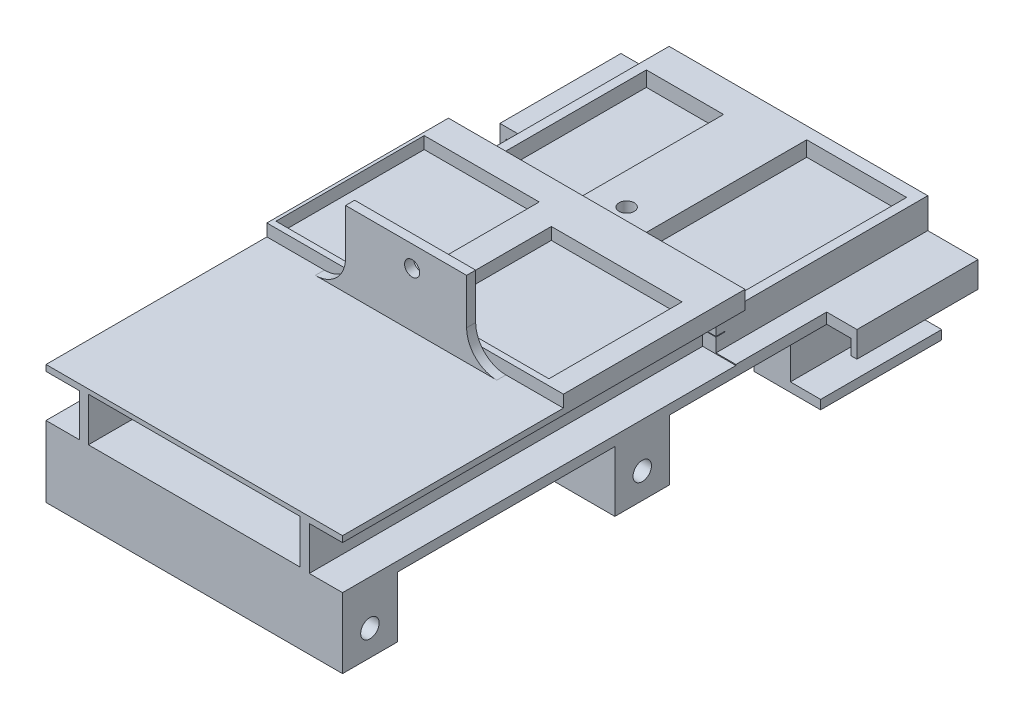
SolidWorks part; units mm, degrees
ref_plane "Front Plane" through (0, 0, 0) normal (0, 0, 1) x (1, 0, 0)
ref_plane "Top Plane" through (0, 0, 0) normal (0, 1, 0) x (1, 0, 0)
ref_plane "Right Plane" through (0, 0, 0) normal (1, 0, 0) x (0, 0, -1)
sketch "Sketch1" plane through (0, 0, 0) normal (0, 1, 0) x (1, 0, 0)
  line L2 (48.0496, -78.5461) -> (-51.9504, -78.5461)
  line L3 (48.0496, -78.5461) -> (48.0496, 121.4539)
  line L4 (48.0496, 121.4539) -> (-51.9504, 121.4539)
  line L5 (-51.9504, -78.5461) -> (-51.9504, 121.4539)
  dimension "D1" = 100
  dimension "D2" = 200
extrude "Boss-Extrude3" add sketch "Sketch1" along normal blind 20
sketch "Sketch2" plane through (0, 0, 78.5461) normal (0, 0, 1) x (1, 0, 0)
  line L0 (-51.9504, 0) -> (48.0496, 0) construction
  line L1 (-36.9504, 18.5) -> (33.0496, 18.5)
  line L2 (-36.9504, 18.5) -> (-36.9504, 4)
  line L3 (-36.9504, 4) -> (33.0496, 4)
  line L4 (33.0496, 18.5) -> (33.0496, 4)
  line L5 (48.0496, 20) -> (48.0496, 0) construction
  dimension "D1" = 14.5
  dimension "D2" = 4
  dimension "D3" = 15
  dimension "D4" = 70
extrude "Cut-Extrude1" cut sketch "Sketch2" against normal blind 125
sketch "Sketch3" plane through (0, 0, -121.4539) normal (0, 0, -1) x (-1, 0, 0)
  line L1 (-48.0496, 0) -> (51.9504, 0)
  line L2 (-48.0496, 0) -> (-48.0496, 20)
  line L3 (-48.0496, 20) -> (51.9504, 20)
  line L4 (51.9504, 0) -> (51.9504, 20)
extrude "Cut-Extrude2" cut sketch "Sketch3" against normal blind 50
sketch "Sketch5" plane through (0, 0, -71.4539) normal (0, 0, -1) x (-1, 0, 0)
  line L1 (-48.0496, 20) -> (51.9504, 20)
  line L2 (-48.0496, 20) -> (-48.0496, 0)
  line L3 (-48.0496, 0) -> (51.9504, 0)
  line L4 (51.9504, 20) -> (51.9504, 0)
extrude "Cut-Extrude4" cut sketch "Sketch5" against normal blind 20
sketch "Sketch6" plane through (0, 0, 78.5461) normal (0, 0, 1) x (1, 0, 0)
  line L0 (-51.9504, 20) -> (-51.9504, 0) construction
  line L1 (-51.9504, 3.9659) -> (-39.9504, 3.9659)
  line L2 (-51.9504, 3.9659) -> (-51.9504, 18)
  line L3 (-51.9504, 18) -> (-39.9504, 18)
  line L4 (-39.9504, 3.9659) -> (-39.9504, 18)
  line L5 (48.0496, 20) -> (48.0496, 0) construction
  line L6 (48.0496, 3.6891) -> (36.0496, 3.6891)
  line L7 (48.0496, 3.6891) -> (48.0496, 18)
  line L8 (48.0496, 18) -> (36.0496, 18)
  line L9 (36.0496, 3.6891) -> (36.0496, 18)
  line L10 (-36.9504, 18.5) -> (-36.9504, 4) construction
  line L11 (-51.9504, 20) -> (48.0496, 20) construction
  line L12 (33.0496, 4) -> (33.0496, 18.5) construction
  dimension "D1" = 3
  dimension "D2" = 2
  dimension "D3" = 2
  dimension "D4" = 3
extrude "Cut-Extrude5" cut sketch "Sketch6" against normal blind 250
sketch "Sketch7" plane through (0, 20, 0) normal (0, 1, 0) x (1, 0, 0)
  line L0 (-51.9504, -78.5461) -> (48.0496, -78.5461) construction
  line L1 (-21.9504, -5.5461) -> (18.0496, -5.5461)
  line L2 (-21.9504, -5.5461) -> (-21.9504, -8.5461)
  line L3 (-21.9504, -8.5461) -> (18.0496, -8.5461)
  line L4 (18.0496, -5.5461) -> (18.0496, -8.5461)
  line L9 (-51.9504, 51.4539) -> (-51.9504, -78.5461) construction
  point P6 (18.0496, -7.0461)
  dimension "D1" = 70
  dimension "D2" = 40
  dimension "D3" = 30
  dimension "D4" = 3
extrude "Boss-Extrude4" add sketch "Sketch7" along normal blind 25
sketch "Sketch8" plane through (0, 0, 5.5461) normal (0, 0, -1) x (-1, 0, 0)
  line L1 (21.9504, 45) -> (21.9504, 20) construction
  line L3 (-18.0496, 20) -> (21.9504, 20) construction
  circle A0 centre (-0.0496, 38) radius 2.5
  dimension "D1" = 22
  dimension "D2" = 18
extrude "Cut-Extrude6" cut sketch "Sketch8" against normal blind 87.3806
fillet "Fillet1" radius 10 2 edges at (18.0496, 20, 7.0461) (-21.9504, 20, 7.0461)
sketch "Sketch9" plane through (0, 20, 0) normal (0, 1, 0) x (1, 0, 0)
  line L0 (48.0496, -78.5461) -> (48.0496, 51.4539) construction
  line L1 (-51.9504, 51.4539) -> (48.0496, 51.4539)
  line L2 (-51.9504, 51.4539) -> (-51.9504, -5.5507)
  line L3 (-51.9504, -5.5507) -> (48.0496, -5.5507)
  line L4 (48.0496, 51.4539) -> (48.0496, -5.5507)
extrude "Boss-Extrude5" add sketch "Sketch9" along normal blind 4
sketch "Sketch10" plane through (0, 24, 0) normal (0, 1, 0) x (1, 0, 0)
  line L0 (-51.9504, 51.4539) -> (-51.9504, -5.5507) construction
  line L1 (-49.9504, -3.5507) -> (-11.9504, -3.5507)
  line L2 (-49.9504, -3.5507) -> (-49.9504, 45.4493)
  line L3 (-49.9504, 45.4493) -> (-11.9504, 45.4493)
  line L4 (-11.9504, -3.5507) -> (-11.9504, 45.4493)
  line L5 (-51.9504, -5.5507) -> (-23.9504, -5.5507) construction
  line L7 (40.2496, -3.5507) -> (-2.9504, -3.5507)
  line L8 (40.2496, -3.5507) -> (40.2496, 40.4493)
  line L9 (40.2496, 40.4493) -> (-2.9504, 40.4493)
  line L10 (-2.9504, -3.5507) -> (-2.9504, 40.4493)
  dimension "D1" = 49
  dimension "D2" = 38
  dimension "D3" = 2
  dimension "D4" = 2
  dimension "D5" = 44
  dimension "D6" = 43.2
  dimension "D7" = 9
extrude "Cut-Extrude7" cut sketch "Sketch10" against normal blind 4
sketch "Sketch11" plane through (0, 0, -51.4539) normal (0, 0, -1) x (-1, 0, 0)
  line L1 (-48.0496, 24) -> (51.9504, 24)
  line L2 (-48.0496, 24) -> (-48.0496, 0)
  line L3 (-48.0496, 0) -> (51.9504, 0)
  line L4 (51.9504, 24) -> (51.9504, 0)
extrude "Boss-Extrude6" add sketch "Sketch11" along normal blind 70
sketch "Sketch12" plane through (-51.9504, 0, 0) normal (-1, 0, 0) x (0, 0, 1)
  line L1 (-121.4539, 24) -> (-54.4539, 24)
  line L2 (-121.4539, 24) -> (-121.4539, 14)
  line L3 (-121.4539, 14) -> (-54.4539, 14)
  line L4 (-54.4539, 24) -> (-54.4539, 14)
  line L5 (-51.4539, 3.9659) -> (-51.4539, 18) construction
  line L6 (-54.4539, 8.5095) -> (-51.4539, 8.5095)
  line L7 (-54.4539, 8.5095) -> (-54.4539, 8.7231)
  line L8 (-54.4539, 8.7231) -> (-51.4539, 8.7231)
  line L9 (-51.4539, 8.5095) -> (-51.4539, 8.7231)
  dimension "D1" = 3
  dimension "D2" = 10
extrude "Cut-Extrude8" cut sketch "Sketch12" against normal blind 200
sketch "Sketch13" plane through (0, 14, 0) normal (0, 1, 0) x (1, 0, 0)
  line L0 (48.0496, 54.4539) -> (-51.9504, 54.4539) construction
  line L1 (-42.0385, 110.9539) -> (-16.5385, 110.9539)
  line L2 (-42.0385, 110.9539) -> (-42.0385, 57.4539)
  line L3 (-42.0385, 57.4539) -> (-16.5385, 57.4539)
  line L4 (-16.5385, 110.9539) -> (-16.5385, 57.4539)
  line L5 (4.4529, 117.4539) -> (37.4529, 117.4539)
  line L6 (4.4529, 117.4539) -> (4.4529, 57.4539)
  line L7 (4.4529, 57.4539) -> (37.4529, 57.4539)
  line L8 (37.4529, 117.4539) -> (37.4529, 57.4539)
  dimension "D1" = 53.5
  dimension "D2" = 25.5
  dimension "D3" = 60
  dimension "D4" = 33
  dimension "D5" = 3
  dimension "D6" = 3
extrude "Cut-Extrude9" cut sketch "Sketch13" against normal blind 5
sketch "Sketch14" plane through (0, 14, 0) normal (0, 1, 0) x (1, 0, 0)
  line L0 (4.4529, 117.4539) -> (4.4529, 57.4539) construction
  circle A0 centre (-6.0471, 68.4392) radius 2.5
  dimension "D1" = 10.5
extrude "Cut-Extrude10" cut sketch "Sketch14" against normal blind 200
sketch "Sketch15" plane through (0, 14, 0) normal (0, 1, 0) x (1, 0, 0)
  line L0 (-51.9504, 121.4539) -> (-51.9504, 54.4539) construction
  line L1 (40.4529, 57.4539) -> (48.0496, 57.4539)
  line L2 (40.4529, 57.4539) -> (40.4529, 121.4539)
  line L3 (40.4529, 121.4539) -> (48.0496, 121.4539)
  line L4 (48.0496, 57.4539) -> (48.0496, 121.4539)
  line L5 (-51.9504, 57.4539) -> (-45.0385, 57.4539)
  line L6 (-51.9504, 57.4539) -> (-51.9504, 121.4539)
  line L7 (-51.9504, 121.4539) -> (-45.0385, 121.4539)
  line L8 (-45.0385, 57.4539) -> (-45.0385, 121.4539)
  line L9 (48.0496, 121.4539) -> (-51.9504, 121.4539) construction
  line L10 (37.4529, 57.4539) -> (37.4529, 117.4539) construction
  line L11 (-42.0385, 110.9539) -> (-42.0385, 57.4539) construction
  dimension "D1" = 3
  dimension "D2" = 3
extrude "Cut-Extrude11" cut sketch "Sketch15" against normal blind 10
sketch "Sketch17" plane through (0, 0, 0) normal (0, -1, 0) x (1, 0, 0)
  line L0 (-51.9504, -121.4539) -> (-51.9504, 78.5461) construction
  line L1 (-51.9504, -121.4539) -> (-26.9504, -121.4539)
  line L2 (-51.9504, -121.4539) -> (-51.9504, -81.4539)
  line L3 (-51.9504, -81.4539) -> (-26.9504, -81.4539)
  line L4 (-26.9504, -121.4539) -> (-26.9504, -81.4539)
  line L6 (48.0496, -121.4539) -> (23.0496, -121.4539)
  line L7 (48.0496, -121.4539) -> (48.0496, -81.4539)
  line L8 (48.0496, -81.4539) -> (23.0496, -81.4539)
  line L9 (23.0496, -121.4539) -> (23.0496, -81.4539)
  dimension "D1" = 25
  dimension "D2" = 40
  dimension "D3" = 25
extrude "Boss-Extrude7" add sketch "Sketch17" along normal blind 25
sketch "Sketch18" plane through (0, 0, -121.4539) normal (0, 0, -1) x (-1, 0, 0)
  line L0 (51.9504, -25) -> (51.9504, 4) construction
  line L5 (-48.0496, 4) -> (-48.0496, -25) construction
  line L6 (-47.0496, 0.5) -> (-28.0496, 0.5)
  line L7 (-47.0496, 0.5) -> (-47.0496, -22)
  line L8 (-47.0496, -22) -> (-28.0496, -22)
  line L9 (-28.0496, 0.5) -> (-28.0496, -22)
  line L10 (-23.0496, -25) -> (-48.0496, -25) construction
  line L11 (32.8714, 0.5) -> (50.9504, 0.5)
  line L12 (32.8714, 0.5) -> (32.8714, -22)
  line L13 (32.8714, -22) -> (50.9504, -22)
  line L14 (50.9504, 0.5) -> (50.9504, -22)
  line L15 (51.9504, -25) -> (26.9504, -25) construction
  line L16 (50.9504, -2.5) -> (51.9504, -2.5)
  line L17 (50.9504, -2.5) -> (50.9504, -19)
  line L18 (50.9504, -19) -> (51.9504, -19)
  line L19 (51.9504, -2.5) -> (51.9504, -19)
  line L21 (-48.0496, -2.5) -> (-47.0496, -2.5)
  line L22 (-48.0496, -2.5) -> (-48.0496, -19)
  line L23 (-48.0496, -19) -> (-47.0496, -19)
  line L24 (-47.0496, -2.5) -> (-47.0496, -19)
  point P18 (51.4504, -2.5)
  dimension "D1" = 19
  dimension "D2" = 22.5
  dimension "D3" = 1
  dimension "D4" = 3
  dimension "D5" = 1
  dimension "D6" = 22.5
  dimension "D7" = 3
  dimension "D8" = 3
  dimension "D9" = 3
extrude "Cut-Extrude12" cut sketch "Sketch18" against normal blind 200 contours L9 L6 L7 L8 | L14 L11 L12 L13 | L22 L23 L24 L21 | L19 L18 L17 L16 region at (37.5496, -10.75, -121.4539) region at (-41.9109, -10.75, -121.4539)
sketch "Sketch20" plane through (0, 0.5, 0) normal (0, -1, 0) x (1, 0, 0)
  line L0 (-32.8714, 78.5461) -> (-32.8714, -121.4539) construction
  line L1 (-50.9504, 78.5461) -> (-32.8714, 78.5461)
  line L2 (-50.9504, 78.5461) -> (-50.9504, 60.4461)
  line L3 (-50.9504, 60.4461) -> (-32.8714, 60.4461)
  line L4 (-32.8714, 78.5461) -> (-32.8714, 60.4461)
  line L5 (-50.9504, 78.5461) -> (-50.9504, -121.4539) construction
  line L6 (-50.9504, -11.4539) -> (-32.8714, -11.4539)
  line L7 (-50.9504, -11.4539) -> (-50.9504, -29.5539)
  line L8 (-50.9504, -29.5539) -> (-32.8714, -29.5539)
  line L9 (-32.8714, -11.4539) -> (-32.8714, -29.5539)
  line L10 (28.0496, 78.5461) -> (28.0496, -121.4539) construction
  line L11 (47.0496, 78.5461) -> (28.0496, 78.5461)
  line L12 (47.0496, 78.5461) -> (47.0496, 60.4461)
  line L13 (47.0496, 60.4461) -> (28.0496, 60.4461)
  line L14 (28.0496, 78.5461) -> (28.0496, 60.4461)
  line L15 (47.0496, 78.5461) -> (47.0496, -121.4539) construction
  line L16 (28.0496, -11.4539) -> (47.0496, -11.4539)
  line L17 (28.0496, -11.4539) -> (28.0496, -29.5539)
  line L18 (28.0496, -29.5539) -> (47.0496, -29.5539)
  line L19 (47.0496, -11.4539) -> (47.0496, -29.5539)
  line L20 (-32.8714, 78.5461) -> (28.0496, 78.5461) construction
  dimension "D1" = 18.1
  dimension "D2" = 18.1
  dimension "D3" = 18.1
  dimension "D4" = 90
  dimension "D5" = 18.1
  dimension "D6" = 90
extrude "Boss-Extrude9" add sketch "Sketch20" along normal blind 20
sketch "Sketch22" plane through (-50.9504, 0, 0) normal (-1, 0, 0) x (0, 0, 1)
  line L0 (-11.4539, 0) -> (-29.5539, 0) construction
  line L1 (78.5461, 0) -> (60.4461, 0) construction
  line L2 (78.5461, -19.5) -> (78.5461, 0) construction
  line L4 (-11.4539, -19.5) -> (-11.4539, 0) construction
  circle A0 centre (-20.5039, -11.5) radius 2.75
  circle A1 centre (69.4961, -11.5) radius 2.75
  dimension "D1" = 11.5
  dimension "D2" = 11.5
  dimension "D3" = 9.05
  dimension "D4" = 9.05
extrude "Boss-Extrude11" add sketch "Sketch22" along normal blind 30
sketch "Sketch24" plane through (47.0496, 0, 0) normal (1, 0, 0) x (0, 0, -1)
  line L0 (-78.5461, 0) -> (-60.4461, 0) construction
  line L1 (-78.5461, -19.5) -> (-78.5461, 0) construction
  line L2 (11.4539, 0) -> (29.5539, 0) construction
  line L3 (11.4539, -19.5) -> (11.4539, 0) construction
  circle A0 centre (20.5039, -11.5) radius 2.75
  circle A1 centre (-69.4961, -11.5) radius 2.75
  dimension "D1" = 11.5
  dimension "D2" = 9.05
  dimension "D3" = 11.5
  dimension "D4" = 9.05
extrude "Boss-Extrude12" add sketch "Sketch24" along normal blind 30
sketch "Sketch25" plane through (-32.8714, 0, 0) normal (-1, 0, 0) x (0, 0, 1)
  line L0 (-121.4539, 0.5) -> (-121.4539, -22) construction
  line L1 (-29.5539, 0.5) -> (-121.4539, 0.5) construction
  circle A0 centre (-109.9539, -11) radius 2.75
  dimension "D1" = 11.5
  dimension "D2" = 11.5
extrude "Cut-Extrude13" cut sketch "Sketch25" against normal blind 200
sketch "Sketch28" plane through (-80.9504, 0, 0) normal (-1, 0, 0) x (0, 0, 1)
  circle A0 centre (-20.5039, -11.5) radius 3.2
  circle A1 centre (69.4961, -11.5) radius 3.2
extrude "Boss-Extrude13" add sketch "Sketch28" along normal blind 1
sketch "Sketch29" plane through (77.0496, 0, 0) normal (1, 0, 0) x (0, 0, -1)
  circle A0 centre (20.5039, -11.5) radius 3.2
  circle A1 centre (-69.4961, -11.5) radius 3.2
extrude "Boss-Extrude14" add sketch "Sketch29" along normal blind 1
sketch "Sketch30" plane through (-81.9504, 0, 0) normal (-1, 0, 0) x (0, 0, 1)
  line L1 (-25.1493, -11) -> (-15.3665, -11)
  line L2 (-25.1493, -11) -> (-25.1493, -12)
  line L3 (-25.1493, -12) -> (-15.3665, -12)
  line L4 (-15.3665, -11) -> (-15.3665, -12)
  line L5 (-21.0039, -6.2254) -> (-20.0039, -6.2254)
  line L6 (-21.0039, -6.2254) -> (-21.0039, -16.3675)
  line L7 (-21.0039, -16.3675) -> (-20.0039, -16.3675)
  line L8 (-20.0039, -6.2254) -> (-20.0039, -16.3675)
  circle A0 centre (-20.5039, -11.5) radius 3.2 construction
  circle M5 centre (-20.5039, -11.5) radius 3.2
  dimension "D5" = 0.5
  dimension "D1" = 1
  dimension "D2" = 1
  dimension "D3" = 0.5
  dimension "D4" = 9.7827
extrude "Cut-Extrude14" cut sketch "Sketch30" against normal blind 10 contours L6 L1 L3 M5 | L1 L8 L3 M5 | L6 L7 L8 L5 region at (-81.9504, -11.5, -22.3474) region at (-81.9504, -11.5, -18.6604)
sketch "Sketch31" plane through (-81.9504, 0, 0) normal (-1, 0, 0) x (0, 0, 1)
  line L1 (64.7483, -11) -> (76.1821, -11)
  line L2 (64.7483, -11) -> (64.7483, -12)
  line L3 (64.7483, -12) -> (76.1821, -12)
  line L4 (76.1821, -11) -> (76.1821, -12)
  line L5 (68.9961, -4.6518) -> (69.9961, -4.6518)
  line L6 (68.9961, -4.6518) -> (68.9961, -17.1131)
  line L7 (68.9961, -17.1131) -> (69.9961, -17.1131)
  line L8 (69.9961, -4.6518) -> (69.9961, -17.1131)
  circle A0 centre (69.4961, -11.5) radius 3.2 construction
  circle M7 centre (69.4961, -11.5) radius 3.2
  dimension "D1" = 1
  dimension "D2" = 1
  dimension "D3" = 0.5
  dimension "D4" = 0.5
extrude "Cut-Extrude15" cut sketch "Sketch31" against normal blind 10 contours L8 L5 L6 M7 | L8 L6 L1 M7 | L8 L1 L6 L3 | L8 L3 L6 M7 | L1 L8 L3 M7 | L6 L1 L3 M7 region at (-81.9504, -11.5, 67.6526) region at (-81.9504, -9.6565, 69.4961) region at (-81.9504, -11.5, 69.4961) region at (-81.9504, -6.4825, 69.4961) region at (-81.9504, -11.5, 71.3396) region at (-81.9504, -13.3435, 69.4961)
sketch "Sketch32" plane through (78.0496, 0, 0) normal (1, 0, 0) x (0, 0, -1)
  line L1 (-74.7242, -11) -> (-64.1753, -11)
  line L2 (-74.7242, -11) -> (-74.7242, -12)
  line L3 (-74.7242, -12) -> (-64.1753, -12)
  line L4 (-64.1753, -11) -> (-64.1753, -12)
  line L5 (-69.9961, -5.2584) -> (-68.9961, -5.2584)
  line L6 (-69.9961, -5.2584) -> (-69.9961, -17.3144)
  line L7 (-69.9961, -17.3144) -> (-68.9961, -17.3144)
  line L8 (-68.9961, -5.2584) -> (-68.9961, -17.3144)
  circle A0 centre (-69.4961, -11.5) radius 3.2 construction
  circle M5 centre (-69.4961, -11.5) radius 3.2
  dimension "D1" = 1
  dimension "D2" = 1
  dimension "D3" = 0.5
  dimension "D4" = 0.5
extrude "Cut-Extrude16" cut sketch "Sketch32" against normal blind 10 contours L8 L6 L1 M5 | L1 L8 L3 M5 | L8 L1 L6 L3 | L6 L1 L3 M5 | L8 L3 L6 M5 region at (78.0496, -11.5, 71.3396) region at (78.0496, -9.6565, 69.4961) region at (78.0496, -11.5, 69.4961) region at (78.0496, -11.5, 67.6526) region at (78.0496, -13.3435, 69.4961)
sketch "Sketch33" plane through (78.0496, 0, 0) normal (1, 0, 0) x (0, 0, -1)
  line L1 (15.4788, -11) -> (26.4195, -11)
  line L2 (15.4788, -11) -> (15.4788, -12)
  line L3 (15.4788, -12) -> (26.4195, -12)
  line L4 (26.4195, -11) -> (26.4195, -12)
  line L5 (20.0039, -6.2366) -> (21.0039, -6.2366)
  line L6 (20.0039, -6.2366) -> (20.0039, -17.1374)
  line L7 (20.0039, -17.1374) -> (21.0039, -17.1374)
  line L8 (21.0039, -6.2366) -> (21.0039, -17.1374)
  circle A1 centre (20.5039, -11.5) radius 3.2 construction
  circle M5 centre (20.5039, -11.5) radius 3.2
  dimension "D1" = 1
  dimension "D2" = 1
  dimension "D3" = 0.5
  dimension "D4" = 0.5
extrude "Cut-Extrude17" cut sketch "Sketch33" against normal blind 10 contours L8 L6 L1 M5 | L8 L1 L6 L3 | L1 L8 L3 M5 | L6 L1 L3 M5 | L8 L3 L6 M5 region at (78.0496, -11.5, -18.6604) region at (78.0496, -9.6565, -20.5039) region at (78.0496, -11.5, -20.5039) region at (78.0496, -11.5, -22.3474) region at (78.0496, -13.3435, -20.5039)
extrude "Cut-Extrude18" cut sketch "Sketch31<3>" against normal blind 20 contours L6 L1 L3 M7 | L8 L1 L6 L3 | L1 L8 L3 M7 | L6 L7 L8 L5 region at (-81.9504, -11.5, 67.6526) region at (-81.9504, -11.5, 69.4961) region at (-81.9504, -11.5, 71.3396)
sketch "Sketch31<3>" plane through (-81.9504, 0, 0) normal (-1, 0, 0) x (0, 0, 1) same geometry as "Sketch31"
extrude "Cut-Extrude19" cut sketch "Sketch30<3>" against normal blind 20 contours L8 L6 L1 M5 | L1 L8 L3 M5 | L6 L1 L3 M5 | L6 L7 L8 L5 region at (-81.9504, -11.5, -22.3474) region at (-81.9504, -9.6565, -20.5039) region at (-81.9504, -11.5, -18.6604)
sketch "Sketch30<3>" plane through (-81.9504, 0, 0) normal (-1, 0, 0) x (0, 0, 1) same geometry as "Sketch30"
extrude "Cut-Extrude20" cut sketch "Sketch32<3>" against normal blind 20 contours L8 L6 L1 M5 | L8 L1 L6 L3 | L1 L8 L3 M5 | L6 L1 L3 M5 | L6 L7 L8 L5 region at (78.0496, -11.5, 71.3396) region at (78.0496, -9.6565, 69.4961) region at (78.0496, -11.5, 69.4961) region at (78.0496, -11.5, 67.6526)
sketch "Sketch32<3>" plane through (78.0496, 0, 0) normal (1, 0, 0) x (0, 0, -1) same geometry as "Sketch32"
extrude "Cut-Extrude21" cut sketch "Sketch33<3>" against normal blind 20 contours L6 L7 L8 L5 | L3 L4 L1 L2
sketch "Sketch33<3>" plane through (78.0496, 0, 0) normal (1, 0, 0) x (0, 0, -1) same geometry as "Sketch33"
sketch "Sketch34" plane through (-81.9504, 0, 0) normal (-1, 0, 0) x (0, 0, 1)
  line L1 (-64.3616, 17.5569) -> (115.9788, 17.5569)
  line L2 (-64.3616, 17.5569) -> (-64.3616, -39.568)
  line L3 (-64.3616, -39.568) -> (115.9788, -39.568)
  line L4 (115.9788, 17.5569) -> (115.9788, -39.568)
extrude "Cut-Extrude22" cut sketch "Sketch34" against normal blind 10
sketch "Sketch35" plane through (78.0496, 0, 0) normal (1, 0, 0) x (0, 0, -1)
  line L1 (-87.8006, 0) -> (44.3807, 0)
  line L2 (-87.8006, 0) -> (-87.8006, -32.6515)
  line L3 (-87.8006, -32.6515) -> (44.3807, -32.6515)
  line L4 (44.3807, 0) -> (44.3807, -32.6515)
extrude "Cut-Extrude23" cut sketch "Sketch35" against normal blind 10
sketch "Sketch37" plane through (-61.9504, 0, 0) normal (-1, 0, 0) x (0, 0, 1)
  circle A0 centre (69.4961, -11.5) radius 3.2
extrude "Boss-Extrude15" add sketch "Sketch37" against normal blind 1
sketch "Sketch38" plane through (-71.9504, 0, 0) normal (-1, 0, 0) x (0, 0, 1)
  circle A0 centre (69.4961, -11.5) radius 3.2
extrude "Boss-Extrude16" add sketch "Sketch38" along normal blind 1
sketch "Sketch39" plane through (-61.9504, 0, 0) normal (-1, 0, 0) x (0, 0, 1)
  circle A0 centre (-20.5039, -11.5) radius 3.2
extrude "Boss-Extrude17" add sketch "Sketch39" against normal blind 1
sketch "Sketch40" plane through (-71.9504, 0, 0) normal (-1, 0, 0) x (0, 0, 1)
  circle A0 centre (-20.5039, -11.5) radius 3.2
extrude "Boss-Extrude18" add sketch "Sketch40" along normal blind 1
sketch "Sketch41" plane through (58.0496, 0, 0) normal (1, 0, 0) x (0, 0, -1)
  circle A0 centre (-69.4961, -11.5) radius 3.2
extrude "Boss-Extrude19" add sketch "Sketch41" against normal blind 1
sketch "Sketch42" plane through (68.0496, 0, 0) normal (1, 0, 0) x (0, 0, -1)
  circle A0 centre (-69.4961, -11.5) radius 3.2
extrude "Boss-Extrude20" add sketch "Sketch42" along normal blind 1
sketch "Sketch43" plane through (58.0496, 0, 0) normal (1, 0, 0) x (0, 0, -1)
  circle A0 centre (20.5039, -11.5) radius 3.2
extrude "Boss-Extrude21" add sketch "Sketch43" against normal blind 1
sketch "Sketch44" plane through (68.0496, 0, 0) normal (1, 0, 0) x (0, 0, -1)
  circle A0 centre (20.5039, -11.5) radius 3.2
extrude "Boss-Extrude22" add sketch "Sketch44" along normal blind 1
extrude "Cut-Extrude24" cut sketch "Sketch30<5>" against normal blind 15 contours L8 L6 L1 M5 | L8 L1 L6 L3 | L8 L3 L6 M5 | L1 L4 L3 L2 region at (-81.9504, -9.6565, -20.5039) region at (-81.9504, -11.5, -20.5039) region at (-81.9504, -13.3435, -20.5039)
sketch "Sketch30<5>" plane through (-81.9504, 0, 0) normal (-1, 0, 0) x (0, 0, 1) same geometry as "Sketch30"
extrude "Cut-Extrude25" cut sketch "Sketch33<4>" against normal blind 15 contours L8 L6 L1 M5 | L8 L1 L6 L3 | L1 L8 L3 M5 | L8 L3 L6 M5 | L1 L4 L3 L2 region at (78.0496, -9.6565, -20.5039) region at (78.0496, -11.5, -20.5039) region at (78.0496, -11.5, -22.3474) region at (78.0496, -13.3435, -20.5039)
sketch "Sketch33<4>" plane through (78.0496, 0, 0) normal (1, 0, 0) x (0, 0, -1) same geometry as "Sketch33"
extrude "Cut-Extrude26" cut sketch "Sketch31<4>" against normal blind 15 contours L8 L6 L1 M7 | L6 L1 L3 M7 | L1 L8 L3 M7 | L6 L7 L8 L5 region at (-81.9504, -11.5, 67.6526) region at (-81.9504, -9.6565, 69.4961) region at (-81.9504, -11.5, 71.3396)
sketch "Sketch31<4>" plane through (-81.9504, 0, 0) normal (-1, 0, 0) x (0, 0, 1) same geometry as "Sketch31"
extrude "Cut-Extrude27" cut sketch "Sketch32<4>" against normal blind 15 contours L8 L6 L1 M5 | L1 L8 L3 M5 | L8 L1 L6 L3 | L6 L1 L3 M5 | L6 L7 L8 L5 region at (78.0496, -11.5, 71.3396) region at (78.0496, -9.6565, 69.4961) region at (78.0496, -11.5, 69.4961) region at (78.0496, -11.5, 67.6526)
sketch "Sketch32<4>" plane through (78.0496, 0, 0) normal (1, 0, 0) x (0, 0, -1) same geometry as "Sketch32"
sketch "Sketch45" plane through (0, 0, 78.5461) normal (0, 0, 1) x (1, 0, 0)
  line L1 (47.0496, -19) -> (73.6486, -19)
  line L2 (47.0496, -19) -> (47.0496, -4.4828)
  line L3 (47.0496, -4.4828) -> (73.6486, -4.4828)
  line L4 (73.6486, -19) -> (73.6486, -4.4828)
  line L6 (47.0496, -4.4828) -> (47.0496, 24.2344)
  line L7 (47.0496, 24.2344) -> (73.6486, 24.2344)
  line L8 (73.6486, -4.4828) -> (73.6486, 24.2344)
  line M4 (47.0496, -19.5) -> (47.0496, 0)
  line M5 (47.0496, 0) -> (48.0496, 0)
  line M6 (48.0496, 0) -> (48.0496, 3.6891)
  line M7 (48.0496, 3.6891) -> (36.0496, 3.6891)
  line M9 (36.0496, 18) -> (48.0496, 18)
  line M10 (48.0496, 18) -> (48.0496, 20)
  line M11 (48.0496, 20) -> (-51.9504, 20)
extrude "Cut-Extrude28" cut sketch "Sketch45" against normal blind 400 contours L3 L8 L7 L6 M11 M10 M9 M7 M6 M5 M4 | L1 L4 L3 M4 region at (60.3491, -11.7414, 78.5461) region at (60.4451, 9.8908, 78.5461)
sketch "Sketch46" plane through (0, 0, 78.5461) normal (0, 0, 1) x (1, 0, 0)
  line L1 (47.0496, 20) -> (56.2317, 20)
  line L2 (47.0496, 20) -> (47.0496, -1.1081)
  line L3 (47.0496, -1.1081) -> (56.2317, -1.1081)
  line L4 (56.2317, 20) -> (56.2317, -1.1081)
extrude "Cut-Extrude29" cut sketch "Sketch46" against normal blind 400
sketch "Sketch47" plane through (0, 0, 78.5461) normal (0, 0, 1) x (1, 0, 0)
  line L1 (-50.9504, -14.25) -> (-87.4394, -14.25)
  line L2 (-50.9504, -14.25) -> (-50.9504, 34.6982)
  line L3 (-50.9504, 34.6982) -> (-87.4394, 34.6982)
  line L4 (-87.4394, -14.25) -> (-87.4394, 34.6982)
  line L5 (-50.9504, -14.25) -> (-87.4394, -14.25)
  line L6 (-50.9504, -14.25) -> (-50.9504, -18.252)
  line L7 (-50.9504, -18.252) -> (-87.4394, -18.252)
  line L8 (-87.4394, -14.25) -> (-87.4394, -18.252)
  line M6 (47.0496, 20) -> (-51.9504, 20)
  line M7 (-51.9504, 20) -> (-51.9504, 18)
  line M8 (-51.9504, 18) -> (-39.9504, 18)
  line M10 (-39.9504, 3.9659) -> (-51.9504, 3.9659)
  line M11 (-51.9504, 3.9659) -> (-51.9504, 0)
  line M12 (-51.9504, 0) -> (-50.9504, 0)
  line M13 (-50.9504, 0) -> (-50.9504, -19.5)
extrude "Cut-Extrude30" cut sketch "Sketch47" against normal blind 400 contours L4 L1 L2 L3 M13 M12 M11 M10 M8 M7 M6 | L1 L8 L7 M13 region at (-69.1949, -16.251, 78.5461) region at (-69.2544, 10.2326, 78.5461)
sketch "Sketch48" plane through (0, 0, 78.5461) normal (0, 0, 1) x (1, 0, 0)
  line L1 (-50.9504, 24) -> (-59.1323, 24)
  line L2 (-50.9504, 24) -> (-50.9504, 0)
  line L3 (-50.9504, 0) -> (-59.1323, 0)
  line L4 (-59.1323, 24) -> (-59.1323, 0)
extrude "Cut-Extrude31" cut sketch "Sketch48" against normal blind 400
sketch "Sketch49" plane through (-32.8714, 0, 0) normal (1, 0, 0) x (0, 0, -1)
  line L1 (-78.5461, 0) -> (-60.4461, 0)
  line L2 (-78.5461, 0) -> (-78.5461, -19.5)
  line L3 (-78.5461, -19.5) -> (-60.4461, -19.5)
  line L4 (-60.4461, 0) -> (-60.4461, -19.5)
extrude "Boss-Extrude23" add sketch "Sketch49" along normal blind 70
sketch "Sketch50" plane through (-32.8714, 0, 0) normal (1, 0, 0) x (0, 0, -1)
  line L1 (11.4539, 0) -> (29.5539, 0)
  line L2 (11.4539, 0) -> (11.4539, -19.5)
  line L3 (11.4539, -19.5) -> (29.5539, -19.5)
  line L4 (29.5539, 0) -> (29.5539, -19.5)
extrude "Boss-Extrude24" add sketch "Sketch50" along normal blind 70
sketch "Sketch51" plane through (-32.8714, 0, 0) normal (-1, 0, 0) x (0, 0, 1)
  line L1 (-121.4539, 0.5) -> (-79.9571, 0.5)
  line L2 (-121.4539, 0.5) -> (-121.4539, -37.5384)
  line L3 (-121.4539, -37.5384) -> (-79.9571, -37.5384)
  line L4 (-79.9571, 0.5) -> (-79.9571, -37.5384)
extrude "Cut-Extrude32" cut sketch "Sketch51" along normal blind 70
sketch "Sketch52" plane through (28.0496, 0, 0) normal (1, 0, 0) x (0, 0, -1)
  line L1 (121.4539, 0.5) -> (73.966, 0.5)
  line L2 (121.4539, 0.5) -> (121.4539, -38.9984)
  line L3 (121.4539, -38.9984) -> (73.966, -38.9984)
  line L4 (73.966, 0.5) -> (73.966, -38.9984)
extrude "Cut-Extrude33" cut sketch "Sketch52" along normal blind 70
sketch "Sketch54" plane through (-32.8714, 0, 0) normal (-1, 0, 0) x (0, 0, 1)
  line L1 (-121.4539, 0.5) -> (-81.4539, 0.5)
  line L2 (-121.4539, 0.5) -> (-121.4539, -25)
  line L3 (-121.4539, -25) -> (-81.4539, -25)
  line L4 (-81.4539, 0.5) -> (-81.4539, -25)
extrude "Boss-Extrude25" add sketch "Sketch54" along normal blind 7
sketch "Sketch56" plane through (-26.9504, 0, 0) normal (1, 0, 0) x (0, 0, -1)
  circle A2 centre (109.9539, -11) radius 3.2188
extrude "Cut-Extrude34" cut sketch "Sketch56" against normal blind 70
sketch "Sketch57" plane through (28.0496, 0, 0) normal (1, 0, 0) x (0, 0, -1)
  line L1 (121.4539, 0.5) -> (81.4539, 0.5)
  line L2 (121.4539, 0.5) -> (121.4539, -25)
  line L3 (121.4539, -25) -> (81.4539, -25)
  line L4 (81.4539, 0.5) -> (81.4539, -25)
extrude "Boss-Extrude26" add sketch "Sketch57" along normal blind 7
sketch "Sketch58" plane through (-26.9504, 0, 0) normal (1, 0, 0) x (0, 0, -1)
  circle A0 centre (109.9539, -11) radius 3.2188
extrude "Cut-Extrude35" cut sketch "Sketch58" along normal blind 90
sketch "Sketch60" plane through (-39.8714, 0, 0) normal (-1, 0, 0) x (0, 0, 1)
  circle A0 centre (-109.9539, -11) radius 3.2188
sketch "Sketch61" plane through (-50.9504, 0, 0) normal (-1, 0, 0) x (0, 0, 1)
  line L0 (-81.4539, 0.5) -> (-121.4539, 0.5) construction
  line L1 (-29.5539, -19.5) -> (-29.5539, 0.5) construction
  line L3 (60.4461, -19.5) -> (60.4461, 0.5) construction
  circle A0 centre (-20.5039, -11) radius 3.05
  circle A2 centre (69.4961, -11) radius 3.05
  dimension "D1" = 11.5
  dimension "D3" = 9.05
  dimension "D2" = 9.05
extrude "Cut-Extrude36" cut sketch "Sketch61" against normal blind 150
sketch "Sketch62" plane through (-50.9504, 0, 0) normal (-1, 0, 0) x (0, 0, 1)
  line L1 (-121.4539, 4) -> (-81.4539, 4)
  line L2 (-121.4539, 4) -> (-121.4539, 0.5)
  line L3 (-121.4539, 0.5) -> (-81.4539, 0.5)
  line L4 (-81.4539, 4) -> (-81.4539, 0.5)
extrude "Boss-Extrude27" add sketch "Sketch62" along normal blind 10
sketch "Sketch64" plane through (47.0496, 0, 0) normal (1, 0, 0) x (0, 0, -1)
  line L1 (121.4539, 4) -> (81.4539, 4)
  line L2 (121.4539, 4) -> (121.4539, 0.5)
  line L3 (121.4539, 0.5) -> (81.4539, 0.5)
  line L4 (81.4539, 4) -> (81.4539, 0.5)
extrude "Boss-Extrude28" add sketch "Sketch64" along normal blind 10
sketch "Sketch65" plane through (0, 0.5, 0) normal (0, -1, 0) x (1, 0, 0)
  line L0 (57.0496, -81.4539) -> (47.0496, -81.4539) construction
  line L1 (57.0496, -121.4539) -> (55.0496, -121.4539)
  line L2 (57.0496, -121.4539) -> (57.0496, -81.4539)
  line L3 (57.0496, -81.4539) -> (55.0496, -81.4539)
  line L4 (55.0496, -121.4539) -> (55.0496, -81.4539)
  line L10 (-60.9504, -81.4539) -> (-50.9504, -81.4539) construction
  line L11 (-60.9504, -121.4539) -> (-58.9504, -121.4539)
  line L12 (-60.9504, -121.4539) -> (-60.9504, -81.4539)
  line L13 (-60.9504, -81.4539) -> (-58.9504, -81.4539)
  line L14 (-58.9504, -121.4539) -> (-58.9504, -81.4539)
  dimension "D1" = 2
  dimension "D2" = 2
extrude "Boss-Extrude29" add sketch "Sketch65" along normal blind 5
sketch "Sketch66" plane through (35.0496, 0, 0) normal (1, 0, 0) x (0, 0, -1)
  line L0 (81.4539, 0.5) -> (81.4539, -25) construction
  line L1 (121.4539, -25) -> (81.4539, -25)
  line L2 (121.4539, -25) -> (121.4539, -22)
  line L3 (121.4539, -22) -> (81.4539, -22)
  line L4 (81.4539, -25) -> (81.4539, -22)
  line L5 (121.4539, 0.5) -> (81.4539, 0.5) construction
  dimension "D1" = 22.5
extrude "Boss-Extrude30" add sketch "Sketch66" along normal blind 10
sketch "Sketch67" plane through (-39.8714, 0, 0) normal (-1, 0, 0) x (0, 0, 1)
  line L0 (-81.4539, -25) -> (-81.4539, 0.5) construction
  line L1 (-121.4539, -25) -> (-81.4539, -25)
  line L2 (-121.4539, -25) -> (-121.4539, -22)
  line L3 (-121.4539, -22) -> (-81.4539, -22)
  line L4 (-81.4539, -25) -> (-81.4539, -22)
  line L5 (-81.4539, 0.5) -> (-121.4539, 0.5) construction
  dimension "D1" = 22.5
extrude "Boss-Extrude31" add sketch "Sketch67" along normal blind 10
sketch "Sketch68" plane through (0, 0, -57.4539) normal (0, 0, -1) x (-1, 0, 0)
  line L1 (-40.4529, 14) -> (-47.0496, 14)
  line L2 (-40.4529, 14) -> (-40.4529, 4)
  line L3 (-40.4529, 4) -> (-47.0496, 4)
  line L4 (-47.0496, 14) -> (-47.0496, 4)
  line L5 (45.0385, 14) -> (50.9504, 14)
  line L6 (45.0385, 14) -> (45.0385, 4)
  line L7 (45.0385, 4) -> (50.9504, 4)
  line L8 (50.9504, 14) -> (50.9504, 4)
extrude "Cut-Extrude37" cut sketch "Sketch68" against normal blind 10
sketch "Sketch69" plane through (0, 0, -51.4539) normal (0, 0, 1) x (1, 0, 0)
  line L0 (36.0496, 18) -> (47.0496, 18) construction
  line L1 (47.0496, 14) -> (40.4529, 14)
  line L2 (47.0496, 14) -> (47.0496, 18)
  line L3 (47.0496, 18) -> (40.4529, 18)
  line L4 (40.4529, 14) -> (40.4529, 18)
  line L6 (-45.0385, 14) -> (-50.9504, 14)
  line L7 (-45.0385, 14) -> (-45.0385, 18)
  line L8 (-45.0385, 18) -> (-50.9504, 18)
  line L9 (-50.9504, 14) -> (-50.9504, 18)
extrude "Cut-Extrude38" cut sketch "Sketch69" against normal blind 10
